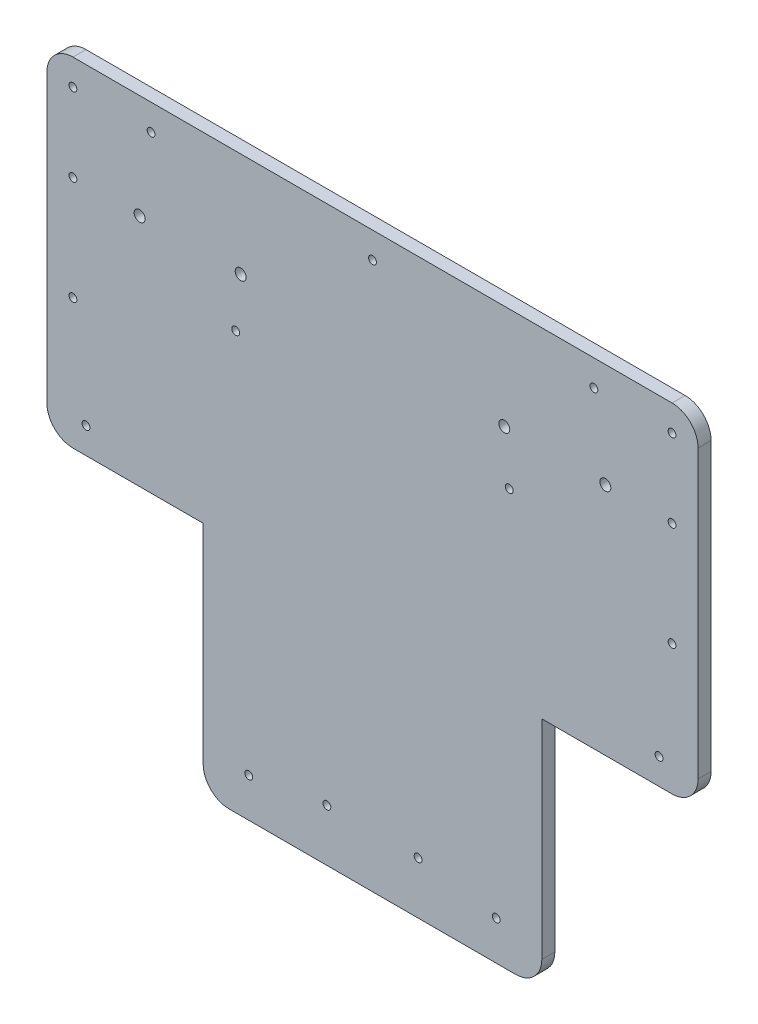
SolidWorks part; units mm, degrees
ref_plane "前视基准面" through (0, 0, 0) normal (0, 0, 1) x (1, 0, 0)
ref_plane "上视基准面" through (0, 0, 0) normal (0, 1, 0) x (1, 0, 0)
ref_plane "右视基准面" through (0, 0, 0) normal (1, 0, 0) x (0, 0, -1)
sketch "草图1" plane through (0, 0, 0) normal (0, 0, 1) x (1, 0, 0)
  line L1 (10, 0) -> (240, 0)
  line L2 (0, -10) -> (0, -210)
  line L3 (10, -220) -> (240, -220)
  line L4 (250, -10) -> (250, -210)
  arc A0 (0, -210) -> (10, -220) centre (10, -210) ccw
  arc A1 (240, -220) -> (250, -210) centre (240, -210) ccw
  arc A2 (240, 0) -> (250, -10) centre (240, -10) cw
  arc A3 (10, 0) -> (0, -10) centre (10, -10) ccw
  point P9 (250, -220)
  point P12 (250, 0)
  point P15 (0, 0)
  dimension "D3" = 10
  dimension "D1" = 250
  dimension "D2" = 220
extrude "凸台-拉伸1" add sketch "草图1" along normal blind 5
sketch "草图7" plane through (0, 0, 0) normal (0, 0, -1) x (-1, 0, 0)
  line L0 (-35.6, -40) -> (0, -40) construction
  line L1 (0, -10) -> (0, -210) construction
  line L2 (-35.6, -40) -> (-35.6, -64.4792) construction
  line L3 (-74.4, -40) -> (-74.4, -67.314) construction
  line L6 (-125, 0) -> (-125, -220) construction
  line L7 (-240, 0) -> (-10, 0) construction
  line L8 (-10, -220) -> (-240, -220) construction
  circle A0 centre (-74.4, -40) radius 2.1 construction
  circle A1 centre (-74.4, -40) radius 2.1
  circle A2 centre (-35.6, -40) radius 2.1 construction
  circle A3 centre (-35.6, -40) radius 2.1
  circle A4 centre (-214.4, -40) radius 2.1
  circle A5 centre (-175.6, -40) radius 2.1
sketch "草图9" plane through (0, 0, 5) normal (0, 0, 1) x (1, 0, 0)
  circle A0 centre (40, -10) radius 1.5 construction
  circle A1 centre (40, -10) radius 1.5
  circle A2 centre (125, -10) radius 1.5 construction
  circle A3 centre (125, -10) radius 1.5
  circle A4 centre (210, -10) radius 1.5 construction
  circle A5 centre (210, -10) radius 1.5
extrude "切除-拉伸7" cut sketch "草图9" against normal up to surface (5 mm away) up to face at (125, -110, 0)
extrude "切除-拉伸8" cut sketch "草图7" against normal up to surface (5 mm away) up to face at (41.5, -10, 5)
sketch "草图10" plane through (0, 0, 5) normal (0, 0, 1) x (1, 0, 0)
  line L0 (250, -210) -> (250, -10) construction
  line L1 (250, -130) -> (190, -130)
  line L2 (250, -130) -> (250, -220)
  line L3 (250, -220) -> (190, -220)
  line L4 (190, -130) -> (190, -220)
  line L5 (10, -220) -> (240, -220) construction
  line L6 (125, 0) -> (125, -235.6988) construction
  line L7 (240, 0) -> (10, 0) construction
  line L8 (60, -130) -> (60, -220)
  line L9 (0, -220) -> (60, -220)
  line L10 (0, -130) -> (0, -220)
  line L11 (0, -130) -> (60, -130)
  dimension "D1" = 60
  dimension "D2" = 90
extrude "切除-拉伸9" cut sketch "草图10" against normal up to next
sketch "草图11" plane through (0, 0, 5) normal (0, 0, 1) x (1, 0, 0)
  line L0 (60, -210) -> (60, -220)
  line L1 (60, -220) -> (70, -220)
  line L2 (190, -210) -> (190, -220)
  line L3 (190, -130) -> (190, -220) construction
  line L4 (60, -220) -> (190, -220) construction
  line L5 (190, -220) -> (180, -220)
  line L6 (0, -120) -> (0, -130)
  line L7 (0, -130) -> (10, -130)
  line L8 (190, -220) -> (190, -130)
  line L9 (190, -130) -> (250, -130)
  line L10 (250, -130) -> (250, -10)
  line L11 (240, 0) -> (10, 0)
  line L12 (0, -10) -> (0, -130)
  line L13 (0, -130) -> (60, -130)
  line L14 (60, -130) -> (60, -220)
  line L15 (60, -220) -> (190, -220)
  line L16 (190, -210) -> (190, -130)
  line L17 (190, -130) -> (240, -130)
  line L18 (250, -120) -> (250, -10)
  line L19 (240, 0) -> (10, 0)
  line L20 (0, -10) -> (0, -120)
  line L21 (10, -130) -> (60, -130)
  line L22 (60, -130) -> (60, -210)
  line L23 (70, -220) -> (180, -220)
  line L24 (250, -120) -> (250, -130)
  line L25 (250, -130) -> (240, -130)
  arc A0 (190, -210) -> (180, -220) centre (180, -210) cw
  arc A1 (60, -210) -> (70, -220) centre (70, -210) ccw
  arc A2 (250, -10) -> (240, 0) centre (240, -10) ccw
  arc A3 (10, 0) -> (0, -10) centre (10, -10) ccw
  arc A4 (250, -10) -> (240, 0) centre (240, -10) ccw
  arc A5 (10, 0) -> (0, -10) centre (10, -10) ccw
  arc A6 (240, -130) -> (250, -120) centre (240, -120) ccw
  arc A7 (0, -120) -> (10, -130) centre (10, -120) ccw
  line M11 (190, -220) -> (190, -130)
  line M12 (190, -130) -> (250, -130)
  line M13 (250, -130) -> (250, -10)
  line M17 (0, -10) -> (0, -130)
  line M18 (0, -130) -> (60, -130)
  line M19 (60, -130) -> (60, -220)
  line M20 (60, -220) -> (190, -220)
  dimension "D2" = 10
  dimension "D3" = 10
  dimension "D1" = 0
extrude "切除-拉伸11" cut sketch "草图11" against normal up to next contours A7 M17 M18 | A1 M19 M20 | A0 M11 M20 | A6 M12 M13 region at (62.2337, -217.7663, 5) region at (2.2337, -127.7663, 5) region at (187.7663, -217.7663, 5) region at (247.7663, -127.7663, 5)
sketch "草图12" plane through (0, 0, 5) normal (0, 0, 1) x (1, 0, 0)
  line L0 (177.5, 0.2469) -> (177.5, -59.7531) construction
  line L1 (177.5, -59.7531) -> (54.2607, -59.7531) construction
  line L2 (162.5, -159) -> (162.5, 30) construction
  line L3 (125, 0) -> (125, -86.6219) construction
  line L4 (240, 0) -> (10, 0) construction
  circle A0 centre (177.5, -59.7531) radius 1.5
  circle A1 centre (142.5, -200) radius 1.5 construction
  circle A2 centre (142.5, -200) radius 1.5
  circle A3 centre (72.5, -59.7531) radius 1.5
  circle A4 centre (107.5, -200) radius 1.5
  dimension "D3" = 3
  dimension "D1" = 60
  dimension "D2" = 15
extrude "切除-拉伸12" cut sketch "草图12" against normal up to next
sketch "草图13" plane through (0, 0, 0) normal (0, 0, -1) x (-1, 0, 0)
  circle A0 centre (-77.5, -205) radius 1.5 construction
  circle A1 centre (-77.5, -205) radius 1.5
  circle A2 centre (-172.5, -205) radius 1.5 construction
  circle A3 centre (-172.5, -205) radius 1.5
  circle A4 centre (-240, -10) radius 1.5 construction
  circle A5 centre (-240, -10) radius 1.5
  circle A6 centre (-10, -10) radius 1.5 construction
  circle A7 centre (-10, -10) radius 1.5
extrude "切除-拉伸13" cut sketch "草图13" against normal up to next
sketch "草图14" plane through (0, 0, 5) normal (0, 0, 1) x (1, 0, 0)
  line L0 (240, -10) -> (240, -122.5975) construction
  line L1 (240, -130) -> (240, -80) construction
  line L2 (240, -130) -> (190, -130) construction
  line L3 (240, -130) -> (240, -40) construction
  line L4 (125, 0) -> (125, -220) construction
  line L5 (240, 0) -> (10, 0) construction
  line L6 (70, -220) -> (180, -220) construction
  circle A0 centre (240, -40) radius 1.5
  circle A1 centre (240, -80) radius 1.5
  circle A2 centre (10, -80) radius 1.5
  circle A3 centre (10, -40) radius 1.5
  dimension "D3" = 3
  dimension "D4" = 3
  dimension "D1" = 50
  dimension "D2" = 90
extrude "切除-拉伸14" cut sketch "草图14" against normal blind 10
sketch "草图15" plane through (0, 0, 5) normal (0, 0, 1) x (1, 0, 0)
  circle A0 centre (235, -120) radius 1.5 construction
  circle A1 centre (235, -120) radius 1.5
  circle A2 centre (15, -120) radius 1.5 construction
  circle A3 centre (15, -120) radius 1.5
extrude "切除-拉伸15" cut sketch "草图15" against normal up to next
